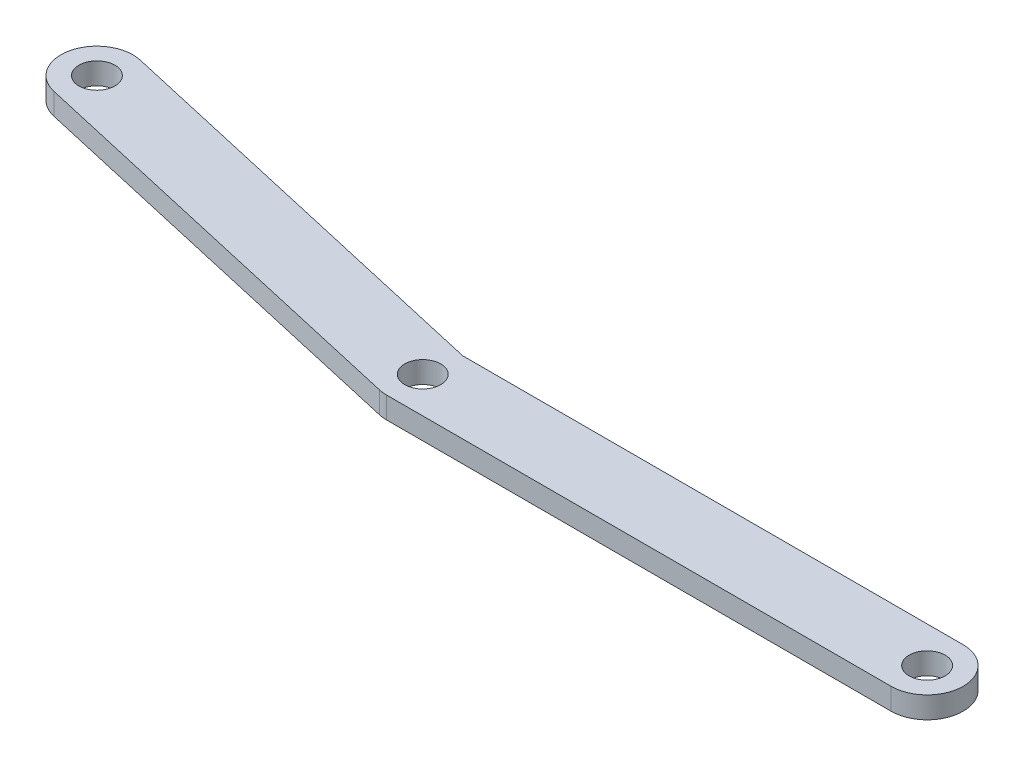
SolidWorks part; units mm, degrees
ref_plane "Front Plane" through (0, 0, 0) normal (0, 0, 1) x (1, 0, 0)
ref_plane "Top Plane" through (0, 0, 0) normal (0, 1, 0) x (1, 0, 0)
ref_plane "Right Plane" through (0, 0, 0) normal (1, 0, 0) x (0, 0, -1)
sketch "Sketch1" plane through (0, 0, 0) normal (0, 1, 0) x (1, 0, 0)
  line L0 (-44.45, 0) -> (44.45, 0) construction
  line L1 (-44.45, 6.35) -> (44.45, 6.35)
  line L2 (-44.45, -6.35) -> (44.45, -6.35)
  arc A0 (-44.45, 6.35) -> (-44.45, -6.35) centre (-44.45, 0) ccw
  arc A1 (44.45, -6.35) -> (44.45, 6.35) centre (44.45, 0) ccw
  circle A3 centre (44.45, 0) radius 3.175
  point P2 (0, 0)
  dimension "D2" = 6.35
  dimension "D4" = 6.35
  dimension "D1" = 88.9
sketch "Sketch2" plane through (0, 0, 0) normal (0, 1, 0) x (1, 0, 0)
  line L0 (-44.45, 0) -> (-118.7564, 16.882) construction
  line L1 (-45.8568, -6.1922) -> (-120.1632, 10.6898)
  line L2 (-43.0432, 6.1922) -> (-117.3495, 23.0742)
  line L3 (-44.45, 0) -> (44.45, 0) construction
  arc A0 (-45.8568, -6.1922) -> (-43.0432, 6.1922) centre (-44.45, 0) ccw
  arc A1 (-117.3495, 23.0742) -> (-120.1632, 10.6898) centre (-118.7564, 16.882) ccw
  circle A2 centre (-118.7564, 16.882) radius 3.175
  point P3 (-81.6032, 8.441)
  dimension "D3" = 6.35
  dimension "D4" = 6.35
  dimension "D1" = 167.2
  dimension "D2" = 76.2
extrude "Boss-Extrude2" add sketch "Sketch2" along normal blind 3.81 contours L2 A1 L1 A0 A2 region at (-80.496, 0, -8.1895)
extrude "Boss-Extrude3" add sketch "Sketch1" along normal blind 3.81 contours L2 A1 L1 A0 A3 region at (-1.15, 0, 0)
sketch "Sketch3" plane through (0, 3.81, 0) normal (0, 1, 0) x (1, 0, 0)
  circle A0 centre (-44.45, 0) radius 3.175
  dimension "D1" = 6.35
extrude "Cut-Extrude1" cut sketch "Sketch3" against normal through all both and the other way through all
